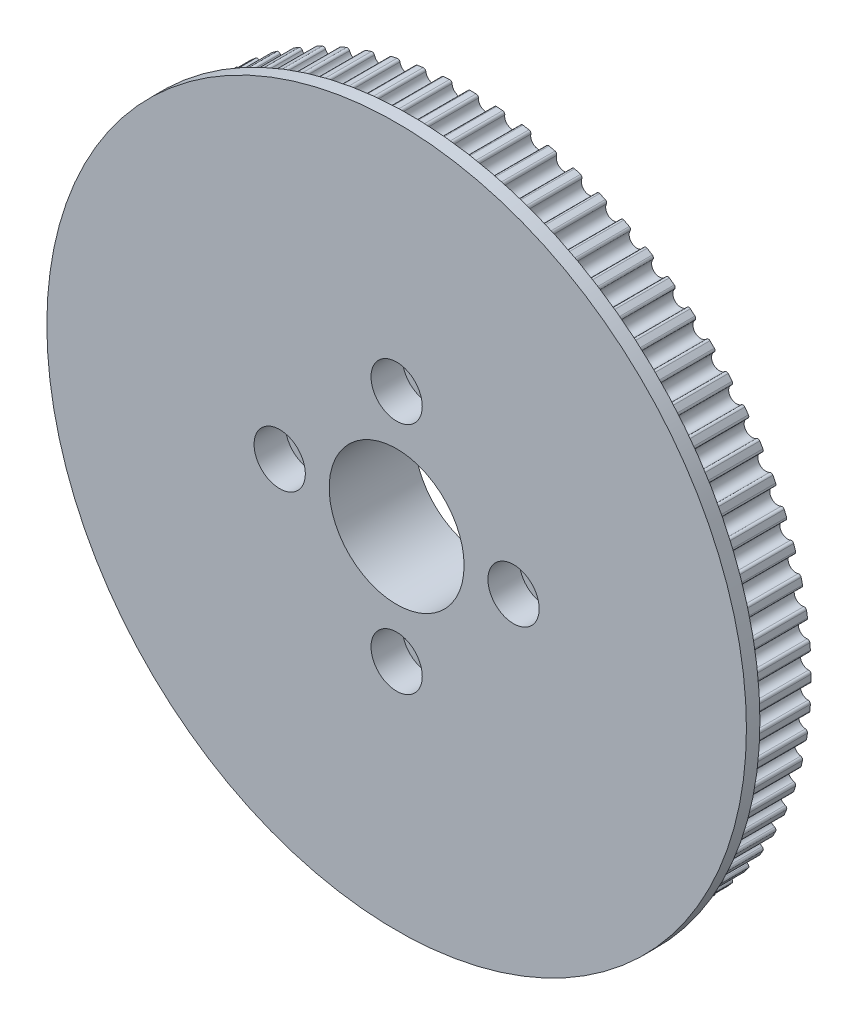
SolidWorks part; units mm, degrees
ref_plane "Front Plane" through (0, 0, 0) normal (1, 0, 0) x (0, 1, 0)
ref_plane "Top Plane" through (0, 0, 0) normal (0, 0, 1) x (0, 1, 0)
ref_plane "Right Plane" through (0, 0, 0) normal (0, 1, 0) x (-1, 0, 0)
sketch "Sketch1" plane through (0, 0, 0) normal (0, 0, 1) x (0, 1, 0)
  line L0 (0, 0) -> (0, 37.5872)
  line L1 (0, 0) -> (1.4297, 36.3891) construction
  line L2 (1.4297, 36.3891) -> (1.4639, 37.2584) construction
  line L3 (0, 0) -> (2.9491, 37.4713)
  arc A3 (0.6561, 37.5815) -> (2.2946, 37.5171) centre (1.4639, 37.2584) ccw
  arc A4 (0, 37.5872) -> (0.6561, 37.5815) centre (0, 0) cw
  arc A5 (2.9491, 37.4713) -> (2.2946, 37.5171) centre (0, 0) ccw
  dimension "D1" = 2.25
  dimension "D2" = 37.5872
  dimension "D3" = 36.4172
  dimension "D4" = 0.87
extrude "Boss-Extrude1" add sketch "Sketch1" along normal blind 7 contours L0 A4 A3 A5 L3
fillet "Fillet1" radius 0.26 2 edges at (-37.5815, 0.6561, 3.5) (-37.5171, 2.2946, 3.5)
pattern_circular "CirPattern1" count 80 over 360 about axis through (0, 0, 7) along (0, 0, -1) of "Fillet1", "Boss-Extrude1" reverse direction yes
sketch "Sketch2" plane through (0, 0, 7) normal (0, 0, 1) x (1, 0, 0)
  circle A1 centre (0, 0) radius 38.8897
  dimension "D2" = 77.7794
extrude "Boss-Extrude2" add sketch "Sketch2" along normal blind 1.5
sketch "Sketch3" plane through (0, 0, 0) normal (0, 0, -1) x (1, 0, 0)
  circle A1 centre (0, 0) radius 21
  dimension "D2" = 42
extrude "Boss-Extrude3" add sketch "Sketch3" along normal blind 1 contours A1
sketch "Sketch4" plane through (0, 0, 8.5) normal (0, 0, 1) x (1, 0, 0)
  circle A0 centre (0, 0) radius 13 construction
  circle A1 centre (0, 13) radius 1.6
  circle A6 centre (0, 13) radius 2.85
  circle A7 centre (13, 0) radius 2.85
  circle A8 centre (13, 0) radius 1.6
  circle A9 centre (0, -13) radius 2.85
  circle A10 centre (0, -13) radius 1.6
  circle A11 centre (-13, 0) radius 2.85
  circle A12 centre (-13, 0) radius 1.6
  point P18 (0, 0)
  dimension "D1" = 26
  dimension "D2" = 3.2
  dimension "D3" = 5.7
extrude "Cut-Extrude3" cut sketch "Sketch4" against normal through all contours A1 | A10 | A12 | A8 region at (0, 13, 8.5) region at (13, 0, 8.5) region at (0, -13, 8.5) region at (-13, 0, 8.5)
extrude "Cut-Extrude4" cut sketch "Sketch4<3>" against normal blind 3.5
sketch "Sketch4<3>" plane through (0, 0, 8.5) normal (0, 0, 1) x (1, 0, 0) same geometry as "Sketch4"
sketch "Sketch5" plane through (0, 0, 8.5) normal (0, 0, 1) x (1, 0, 0)
  circle A0 centre (0, 0) radius 7.5
  dimension "D1" = 15
extrude "Cut-Extrude5" cut sketch "Sketch5" against normal blind 10 contours A0
equation "\"D1@Sketch1\"=360 / \"Teeth\" / 2"
equation "\"Teeth\"= 80"
equation "\"D2@Sketch1\"= \"Teeth\" * 3 / 2 / PI - 0.61"
equation "\"D3@Sketch1\"=\"D2@Sketch1\" - 1.17"
equation "\"D4@Sketch1\"=1.74/2"
equation "\"D2@Sketch2\"=\"Teeth\" * 3 / PI - 0.615 + 2"
